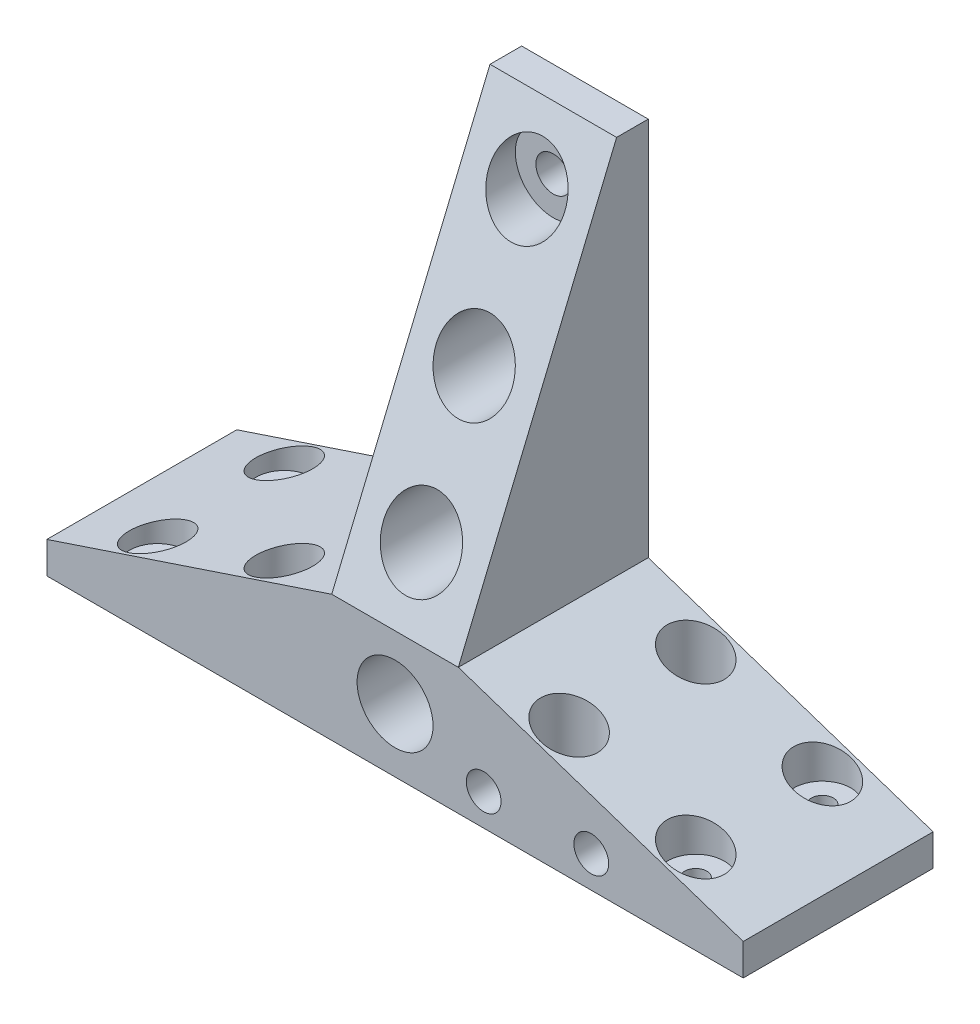
SolidWorks part; units mm, degrees
ref_plane "Plan de face" through (0, 0, 0) normal (0, 0, 1) x (1, 0, 0)
ref_plane "Plan de dessus" through (0, 0, 0) normal (0, 1, 0) x (1, 0, 0)
ref_plane "Plan de droite" through (0, 0, 0) normal (1, 0, 0) x (0, 0, -1)
sketch "Esquisse1" plane through (0, 0, 0) normal (0, 0, 1) x (1, 0, 0)
  line L1 (-9.5845, 32.7642) -> (10.4155, 32.7642)
  line L2 (-9.5845, 32.7642) -> (-9.5845, -47.2358)
  line L3 (-9.5845, -47.2358) -> (10.4155, -47.2358)
  line L4 (10.4155, 32.7642) -> (10.4155, -47.2358)
  circle A0 centre (0.4155, 22.7642) radius 2.75
  circle A1 centre (0.4155, -17.2358) radius 2.75
  circle A2 centre (0.4155, 2.7642) radius 2.75
  circle A3 centre (0.4155, -37.2358) radius 2.75
  point P13 (0.4155, -47.2358)
  dimension "D3" = 5.5
  dimension "D1" = 20
  dimension "D2" = 80
  dimension "D4" = 10
  dimension "D5" = 20
  dimension "D6" = 10
  dimension "D7" = 20
extrude "Boss.-Extru.1" add sketch "Esquisse1" along normal blind 5
sketch "Esquisse3" plane through (0, 0, 5) normal (0, 0, 1) x (1, 0, 0)
  line L0 (-9.5845, -47.2358) -> (-54.5845, -47.2358)
  line L1 (-54.5845, -47.2358) -> (-54.5845, -42.2358)
  line L2 (-54.5845, -42.2358) -> (-9.5845, -27.2358)
  line L3 (-9.5845, 32.7642) -> (-9.5845, -47.2358) construction
  line L4 (-9.5845, -27.2358) -> (-9.5845, -47.2358)
  line L5 (10.4155, -47.2358) -> (55.4155, -47.2358)
  line L6 (55.4155, -47.2358) -> (55.4155, -42.2358)
  line L7 (55.4155, -42.2358) -> (10.4155, -27.2358)
  line L8 (10.4155, -47.2358) -> (10.4155, 32.7642) construction
  line L9 (10.4155, -27.2358) -> (10.4155, -47.2358)
  dimension "D1" = 5
  dimension "D2" = 45
  dimension "D3" = 20
extrude "Boss.-Extru.2" add sketch "Esquisse3" against normal blind 5
sketch "Esquisse4" plane through (0, 0, 5) normal (0, 0, 1) x (1, 0, 0)
  line L0 (55.4155, -47.2358) -> (55.4155, -42.2358) construction
  line L1 (55.4155, -42.2358) -> (10.4155, -27.2358) construction
  line L2 (-9.5845, -27.2358) -> (-54.5845, -42.2358) construction
  line L3 (-54.5845, -42.2358) -> (-54.5845, -47.2358) construction
  line L4 (-54.5845, -47.2358) -> (55.4155, -47.2358) construction
  line L5 (55.4155, -47.2358) -> (55.4155, -42.2358)
  line L6 (55.4155, -42.2358) -> (10.4155, -27.2358)
  line L7 (-9.5845, -27.2358) -> (-54.5845, -42.2358)
  line L8 (-54.5845, -42.2358) -> (-54.5845, -47.2358)
  line L9 (-54.5845, -47.2358) -> (55.4155, -47.2358)
  line L10 (-9.5845, -27.2358) -> (10.4155, -27.2358)
  circle A0 centre (0.4155, -37.2358) radius 2.75 construction
  circle A1 centre (0.4155, -37.2358) radius 2.75
extrude "Boss.-Extru.3" add sketch "Esquisse4" along normal blind 25
sketch "Esquisse5" plane through (-9.5845, 0, 0) normal (-1, 0, 0) x (0, 0, 1)
  line L0 (5, -27.2358) -> (30, -27.2358)
  line L1 (30, -27.2358) -> (5, 32.7642)
  line L2 (5, 32.7642) -> (5, -27.2358)
extrude "Boss.-Extru.4" add sketch "Esquisse5" against normal up to surface (20 mm away) up to face at (10.4155, 2.7642, 2.5)
sketch "Esquisse6" plane through (0, 0, 5) normal (0, 0, -1) x (-1, 0, 0)
  circle A0 centre (-0.4155, 2.7642) radius 6
  circle A1 centre (-0.4155, -17.2358) radius 6
  circle A2 centre (-0.4155, 22.7642) radius 6
  circle A3 centre (-0.4155, -37.2358) radius 6
  dimension "D1" = 12
extrude "Enlèv. mat.-Extru.1" cut sketch "Esquisse6" against normal up to next
sketch "Esquisse7" plane through (0, -47.2358, 0) normal (0, -1, 0) x (1, 0, 0)
  line L0 (-42.0845, 25) -> (-22.0845, 25) construction
  line L1 (-22.0845, 25) -> (-22.0845, 5) construction
  line L2 (-54.5845, 0) -> (-54.5845, 30) construction
  line L3 (22.9155, 5) -> (22.9155, 25) construction
  line L4 (22.9155, 25) -> (42.9155, 25) construction
  line L5 (55.4155, 0) -> (55.4155, 30) construction
  circle A0 centre (-42.0845, 25) radius 1.75
  circle A1 centre (-22.0845, 25) radius 1.75
  circle A2 centre (-22.0845, 5) radius 1.75
  circle A3 centre (-42.0845, 5) radius 1.75
  circle A4 centre (42.9155, 25) radius 1.75
  circle A5 centre (42.9155, 5) radius 1.75
  circle A6 centre (22.9155, 5) radius 1.75
  circle A7 centre (22.9155, 25) radius 1.75
  point P8 (-22.0845, 15)
  point P11 (-54.5845, 15)
  point P12 (-32.0845, 25)
  point P21 (22.9155, 15)
  point P24 (55.4155, 15)
  point P25 (32.9155, 25)
  dimension "D1" = 3.5
  dimension "D4" = 3.5
  dimension "D2" = 20
  dimension "D3" = 22.5
  dimension "D5" = 20
  dimension "D6" = 22.5
extrude "Enlèv. mat.-Extru.2" cut sketch "Esquisse7" against normal up to next
ref_plane "Plan3" through (0, -42.2358, 0) normal (0, -1, 0) x (-1, 0, 0)
sketch "Esquisse9" plane through (0, -42.2358, 0) normal (0, -1, 0) x (-1, 0, 0)
  circle A0 centre (42.0845, -25) radius 4.5
  circle A1 centre (22.0845, -25) radius 4.5
  circle A2 centre (22.0845, -5) radius 4.5
  circle A3 centre (42.0845, -5) radius 4.5
  circle A4 centre (-22.9155, -25) radius 4.5
  circle A5 centre (-42.9155, -25) radius 4.5
  circle A6 centre (-42.9155, -5) radius 4.5
  circle A7 centre (-22.9155, -5) radius 4.5
  dimension "D1" = 9
extrude "Enlèv. mat.-Extru.3" cut sketch "Esquisse9" against normal up to next
sketch "Esquisse10" plane through (0, 0, 30) normal (0, 0, 1) x (1, 0, 0)
  line L0 (24.6655, -42.2358) -> (21.1655, -42.2358) construction
  line L1 (24.6655, -42.2358) -> (21.1655, -42.2358) construction
  line L2 (31.4155, -42.2358) -> (14.4155, -42.2358) construction
  circle A0 centre (14.4155, -42.2358) radius 2.75
  circle A1 centre (31.4155, -42.2358) radius 2.75
  point P7 (22.9155, -42.2358)
  point P8 (22.9155, -42.2358)
  dimension "D1" = 5.5
  dimension "D2" = 17
extrude "Enlèv. mat.-Extru.4" cut sketch "Esquisse10" against normal up to next
